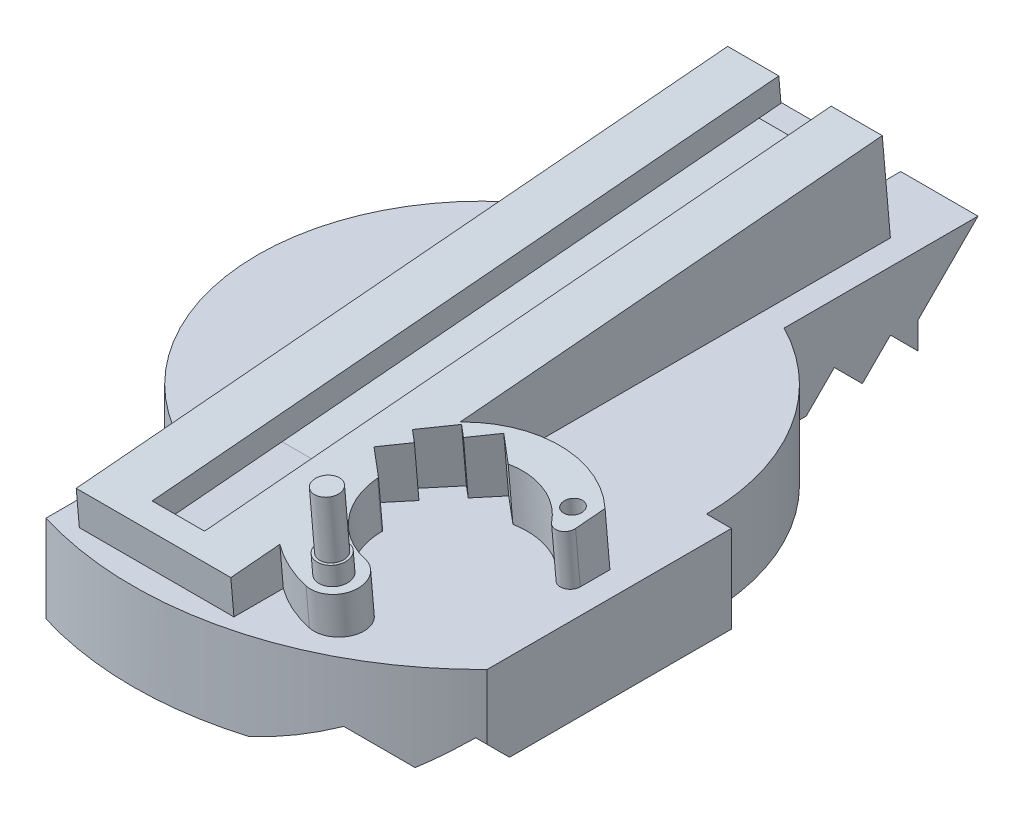
SolidWorks part; units mm, degrees
material "PLA"
ref_plane "Plan de face" through (0, 0, 0) normal (0, 0, 1) x (1, 0, 0)
ref_plane "Plan de dessus" through (0, 0, 0) normal (0, 1, 0) x (1, 0, 0)
ref_plane "Plan de droite" through (0, 0, 0) normal (1, 0, 0) x (0, 0, -1)
sketch "Esquisse1" plane through (0, 0, 0) normal (0, 1, 0) x (1, 0, 0)
  line L1 (-50, -70) -> (50, -70)
  line L2 (-50, -70) -> (-50, 70)
  line L3 (-50, 70) -> (50, 70)
  line L4 (50, -70) -> (50, 70)
  line L5 (-50, -70) -> (50, 70) construction
  line L6 (-50, 70) -> (50, -70) construction
  circle A0 centre (0, 0) radius 45
  point P0 (0, 0)
  dimension "D3" = 90
  dimension "D1" = 100
  dimension "D2" = 140
extrude "Boss.-Extru.1" add sketch "Esquisse1" along normal blind 12.5
sketch "Esquisse3" plane through (0, 12.5, 0) normal (0, 1, 0) x (1, 0, 0)
  line L1 (-50, -70) -> (50, -70)
  line L2 (-50, -70) -> (-50, 70)
  line L3 (-50, 70) -> (50, 70)
  line L4 (50, -70) -> (50, 70)
extrude "Boss.-Extru.2" add sketch "Esquisse3" along normal blind 5
sketch "Esquisse5" plane through (0, 17.5, 0) normal (0, 1, 0) x (1, 0, 0)
  line L0 (50, 0) -> (-50, 0) construction
  line L1 (50, -70) -> (50, 70) construction
  line L2 (-50, 70) -> (-50, -70) construction
ref_plane "Plan1" through (0, 0.1329, -1.5194) normal (0, 0.0872, -0.9962) x (-1, 0, 0)
sketch "Esquisse14" plane through (0, 17.5, 0) normal (0, 1, 0) x (1, 0, 0)
  line L0 (50, -30) -> (-50, -30) construction
  line L1 (50, -70) -> (50, 70) construction
  line L2 (-50, 70) -> (-50, -70) construction
  dimension "D1" = 30
ref_plane "Plan2" through (0, 19.9718, 1.7473) normal (0, -0.9962, -0.0872) x (-1, 0, 0)
sketch "Esquisse15" plane through (0, 9.8574, 117.3553) normal (0, 0.9962, 0.0872) x (1, 0, 0)
  line L0 (50, 87.689) -> (-50, 87.689) construction
  line L1 (-15.5, 87.689) -> (15.5, 87.689)
  line L2 (-15.5, 87.689) -> (-15.5, 183.689)
  line L3 (-15.5, 183.689) -> (15.5, 183.689)
  line L4 (15.5, 87.689) -> (15.5, 183.689)
  point P7 (0, 87.689)
  dimension "D1" = 31
  dimension "D2" = 96
extrude "Boss.-Extru.6" add sketch "Esquisse15" against normal up to surface up to face at (0, 17.5, 0)
sketch "Esquisse6" plane through (0, -4.4235, -1.9181) normal (0, -0.0872, 0.9962) x (1, 0, 0)
  line L0 (50, 22.0072) -> (-50, 22.0072) construction
  line L6 (15.5, 24.6219) -> (10.5, 24.6219)
  line L7 (15.5, 24.6219) -> (15.5, 34.8719)
  line L8 (15.5, 34.8719) -> (5.25, 34.8719)
  line L11 (5.25, 29.8719) -> (5.25, 34.8719)
  line L15 (0, -1.5271) -> (0, 34.8719) construction
  line L16 (50, -1.5271) -> (-50, -1.5271) construction
  line L17 (-5.25, 29.8719) -> (-5.25, 34.8719)
  line L18 (-15.5, 34.8719) -> (-5.25, 34.8719)
  line L19 (-15.5, 24.6219) -> (-15.5, 34.8719)
  line L20 (-15.5, 24.6219) -> (-10.5, 24.6219)
  line L23 (10.5, 24.6219) -> (5.25, 29.8719)
  line L24 (-5.25, 29.8719) -> (-10.5, 24.6219)
  line L26 (-15.5, 24.6219) -> (15.5, 24.6219) construction
  dimension "D1" = 10.25
  dimension "D2" = 5
  dimension "D3" = 5
  dimension "D4" = 45
  dimension "D5" = 10.5
extrude "Boss.-Extru.3" add sketch "Esquisse6" along normal blind 60 and the other way up to surface (66.1142 mm away) other way up to face at (0, 21.6835, -66.0007)
sketch "Esquisse7" plane through (0, -5.0964, 58.2523) normal (0, -0.0872, 0.9962) x (1, 0, 0)
  line L1 (-15.5, 30.2981) -> (15.5, 30.2981)
  line L2 (-15.5, 30.2981) -> (-15.5, 22.6827)
  line L3 (-15.5, 22.6827) -> (15.5, 22.6827)
  line L4 (15.5, 30.2981) -> (15.5, 22.6827)
extrude "Boss.-Extru.4" add sketch "Esquisse7" along normal blind 5
sketch "Esquisse16" plane through (0, 5.8952, -67.382) normal (0, 0.0872, -0.9962) x (-1, 0, 0)
  line L0 (-10.5, 20.0481) -> (-5.25, 25.2981)
  line L1 (-5.25, 25.2981) -> (-5.25, 30.2981)
  line L2 (-5.25, 30.2981) -> (5.25, 30.2981)
  line L3 (5.25, 30.2981) -> (5.25, 25.2981)
  line L4 (5.25, 25.2981) -> (10.5, 20.0481)
  line L5 (10.5, 20.0481) -> (-10.5, 20.0481)
extrude "Enlèv. mat.-Extru.3" cut sketch "Esquisse16" against normal up to surface (126.1142 mm away) up to face at (0, 20.8973, 60.5264)
chamfer "Chanfrein1" distance 13 angle 45 1 edges at (0, 12.5, 45)
sketch "Esquisse18" plane through (0, 12.5, 0) normal (0, -1, 0) x (-1, 0, 0)
  line L1 (-2.75, -1.5) -> (2.75, -1.5)
  line L2 (-2.75, -1.5) -> (-2.75, 1.5)
  line L3 (-2.75, 1.5) -> (2.75, 1.5)
  line L4 (2.75, -1.5) -> (2.75, 1.5)
  line L5 (-2.75, -1.5) -> (2.75, 1.5) construction
  line L6 (-2.75, 1.5) -> (2.75, -1.5) construction
  point P0 (0, 0)
  dimension "D1" = 3
  dimension "D2" = 5.5
extrude "Enlèv. mat.-Extru.5" cut sketch "Esquisse18" against normal blind 10
chamfer "Chanfrein2" distance 2 angle 45 2 edges at (0, 12.5, 1.5) (0, 12.5, -1.5)
sketch "Esquisse12" plane through (0, 17.5, 0) normal (0, 1, 0) x (1, 0, 0)
  line L0 (-15.5, 66.3667) -> (-15.5, -65.2483) construction
  line L5 (-50, 70) -> (-50, -70)
  line L6 (-50, -70) -> (-20.5, -70)
  line L10 (-20.5, 40.0593) -> (-20.5, 70)
  line L11 (-50, -70) -> (50, -70) construction
  line L12 (-20.5, -40.0593) -> (-20.5, -70)
  line L17 (0, -70) -> (0, 70) construction
  line L21 (-20.5, 70) -> (-50, 70)
  line L24 (-50, 70) -> (-50, -70) construction
  line L26 (50, 70) -> (-50, 70) construction
  line L32 (50, 70) -> (20.5, 70)
  line L33 (50, 70) -> (50, 0)
  line L34 (50, 0) -> (45, 0)
  line L35 (20.5, 70) -> (20.5, 40.0593)
  arc A1 (-20.5, 40.0593) -> (-20.5, -40.0593) centre (0, 0) ccw
  arc A3 (20.5, 40.0593) -> (45, 0) centre (0, 0) cw
  dimension "D3" = 45
  dimension "D1" = 5
extrude "Enlèv. mat.-Extru.1" cut sketch "Esquisse12" against normal through all both and the other way through all
sketch "Esquisse13" plane through (0, 0, 0) normal (1, 0, 0) x (0, 0, -1)
  line L0 (67, 0) -> (61.375, 5.625)
  line L1 (40.0593, 0) -> (70, 0) construction
  line L2 (61.375, 5.625) -> (55.75, 0)
  line L3 (55.75, 0) -> (50.125, 5.625)
  line L4 (50.125, 5.625) -> (44.5, 0)
  line L5 (-40.0593, 0) -> (40.0593, 0) construction
  line L6 (44.5, 0) -> (55.75, 0)
  line L7 (67, 0) -> (55.75, 0)
  line L9 (70, 0) -> (70, 17.5) construction
  line L10 (-44.5, 0) -> (44.5, 0) construction
  line L11 (0, 0) -> (0, 6.324) construction
  line L13 (-44.5, 0) -> (-55.75, 0)
  line L14 (-67, 0) -> (-55.75, 0)
  line L16 (-50.125, 5.625) -> (-44.5, 0)
  line L17 (-55.75, 0) -> (-50.125, 5.625)
  line L18 (-61.375, 5.625) -> (-55.75, 0)
  line L19 (-67, 0) -> (-61.375, 5.625)
  dimension "D1" = 3
  dimension "D3" = 45
extrude "Enlèv. mat.-Extru.2" cut sketch "Esquisse13" against normal through all both and the other way through all contours L17 L13 L16 | L19 L14 L18 | L3 L4 L6 | L7 L0 L2 region at (0, 1.875, 61.375) region at (0, 1.875, 50.125)
sketch "Esquisse17" plane through (0, 19.9718, 1.7473) normal (0, 0.9962, 0.0872) x (1, 0, 0)
  line L0 (15.5, 67.6394) -> (-15.5, 67.6394) construction
  line L1 (3.2, 62.9394) -> (-3.2, 62.9394)
  line L2 (3.2, 62.9394) -> (3.2, 66.3394)
  line L3 (3.2, 66.3394) -> (-3.2, 66.3394)
  line L4 (-3.2, 62.9394) -> (-3.2, 66.3394)
  line L5 (3.2, 62.9394) -> (-3.2, 66.3394) construction
  line L6 (3.2, 66.3394) -> (-3.2, 62.9394) construction
  point P0 (0, 64.6394)
  dimension "D1" = 3.4
  dimension "D2" = 3
  dimension "D3" = 6.4
extrude "Enlèv. mat.-Extru.4" cut sketch "Esquisse17" against normal blind 5
chamfer "Chanfrein3" distance 0.5 angle 45 4 edges at (3.2, 25.6055, -62.6461) (0, 25.4573, -60.9526) (0, 25.7536, -64.3396) (-3.2, 25.6055, -62.6461)
ref_axis "Axe1" through (0, 37.8818, 0) along (0, -1, 0)
sketch "Esquisse19" plane through (0, 17.5, 0) normal (0, 1, 0) x (1, 0, 0)
  line L0 (20.5, 66.9309) -> (-20.5, 66.9309)
  line L1 (20.5, 40.0593) -> (20.5, 70) construction
  line L2 (-20.5, 70) -> (-20.5, 40.0593) construction
  line L4 (20.5, 70) -> (-20.5, 70) construction
  arc A0 (-20.5, 66.9309) -> (20.5, 66.9309) centre (0, 0) ccw
extrude "Enlèv. mat.-Extru.6" cut sketch "Esquisse19" against normal through all flip side to cut
sketch "Esquisse20" plane through (0, 19.9718, 1.7473) normal (0, -0.9962, -0.0872) x (-1, 0, 0)
  line L1 (-27.3919, -19.5971) -> (-22.0295, -15.0976)
  line L3 (-15.5003, -33.7689) -> (-10.138, -29.2694)
  line L4 (-22.0295, -15.0976) -> (-18.3335, -19.5024)
  line L5 (-15.5, -63.4748) -> (-15.5, 67.6394) construction
  line L6 (-13.834, -24.8647) -> (-11.5359, -22.9363)
  line L7 (-50, -28.3606) -> (50, -28.3606) construction
  line L8 (-30, -33.8606) -> (-67.0315, -33.8606) construction
  line L9 (-18.3335, -19.5024) -> (-16.0354, -17.574)
  line L10 (-11.5359, -22.9363) -> (-16.0354, -17.574)
  line L11 (-30, -33.8606) -> (-11.0095, -17.9257) construction
  line L12 (-13.834, -24.8647) -> (-10.138, -29.2694)
  arc A0 (-27.3919, -19.5971) -> (-15.5003, -33.7689) centre (-30, -33.8606) ccw
  dimension "D1" = 14.5
  dimension "D4" = 5.5
  dimension "D2" = 18.5
  dimension "D3" = 7
  dimension "D5" = 40
  dimension "D6" = 7
  dimension "D7" = 3
extrude "Enlèv. mat.-Extru.7" cut sketch "Esquisse20" against normal through all and the other way blind 10
sketch "Esquisse21" plane through (0, 30.1828, 2.6407) normal (0, 0.9962, 0.0872) x (1, 0, 0)
  line L7 (45, -17.7667) -> (45, -23.6989)
  line L9 (62.3467, -18.0505) -> (62.3467, -56.0213) construction
  line L10 (35.8082, -55.0804) -> (62.3467, -56.0213) construction
  line L11 (34.809, -47.5402) -> (54.8467, -48.2507) construction
  line L12 (54.8467, -25.5505) -> (54.8467, -48.2507) construction
  line L13 (41.8828, -25.5505) -> (54.8467, -25.5505) construction
  line L14 (45.2988, -18.0505) -> (62.3467, -18.0505) construction
  line L15 (22.0295, -15.0976) -> (18.3335, -19.5024)
  line L16 (22.0295, -15.0976) -> (27.3916, -19.5969)
  line L17 (10.5, -29.5732) -> (15.5, -33.7687)
  line L18 (15.5, -33.7687) -> (15.5, -63.4748) construction
  line L19 (27.3919, -19.5971) -> (22.0295, -15.0976) construction
  line L20 (13.834, -24.8647) -> (11.1117, -22.5804)
  line L21 (18.3335, -19.5024) -> (16.0354, -17.574)
  line L22 (18.3335, -19.5024) -> (16.0354, -17.574) construction
  line L23 (13.834, -24.8647) -> (11.5359, -22.9363) construction
  line L24 (13.834, -24.8647) -> (10.5, -28.838)
  line L25 (15.5, -18.212) -> (16.0354, -17.574)
  line L26 (15.5, 67.6394) -> (15.5, -18.212) construction
  line L27 (15.5, -18.212) -> (15.5, -17.3148)
  line L28 (10.5, -48.6935) -> (10.5, -29.5732)
  line L29 (10.5, -29.5732) -> (10.5, -58.4748) construction
  line L30 (10.5, -28.838) -> (10.5, -23.6742)
  arc A0 (41.4243, -24.9306) -> (27.3916, -19.5969) centre (30, -33.8606) ccw
  arc A1 (11.1117, -22.5804) -> (10.5, -23.6742) centre (30, -33.8606) ccw
  arc A2 (45, -17.7667) -> (15.5, -17.3148) centre (30, -33.8606) ccw
  arc A3 (45.2988, -18.0505) -> (35.8082, -55.0804) centre (30, -33.8606) ccw construction
  arc A4 (41.8828, -25.5505) -> (34.809, -47.5402) centre (30, -33.8606) ccw construction
  arc A5 (45, -23.6989) -> (41.4243, -24.9306) centre (43, -23.6989) cw
  arc A6 (27.0256, -48.0526) -> (24.9744, -57.8399) centre (26, -52.9462) cw
  arc A7 (15.5, -33.7687) -> (27.0256, -48.0526) centre (30, -33.8606) ccw
  arc A8 (15.5, -33.8606) -> (27.3919, -19.5971) centre (30, -33.8606) ccw construction
  arc A10 (10.5, -48.6935) -> (24.9744, -57.8399) centre (30, -33.8606) ccw
  point P17 (26, -55.4918)
  point P32 (0, 0)
  dimension "D2" = 2
  dimension "D5" = 22.0003
  dimension "D6" = 5
  dimension "D3" = 15
  dimension "D4" = 4
  dimension "D1" = 7.5
extrude "Boss.-Extru.7" add sketch "Esquisse21" against normal up to surface (11.025 mm away) up to face at (9.7392, 17.5, -5.7302)
sketch "Esquisse22" plane through (0, 30.1828, 2.6407) normal (0, 0.9962, 0.0872) x (1, 0, 0)
  line L0 (18.7512, -47.2664) -> (41.2488, -20.4548) construction
  line L1 (30, -33.8606) -> (30, -23.5783) construction
  circle A0 centre (41.2488, -20.4548) radius 1.9
  circle A1 centre (18.7512, -47.2664) radius 1.9
  arc A3 (41.4243, -24.9306) -> (27.3916, -19.5969) centre (30, -33.8606) ccw construction
  point P4 (30, -33.8606)
  point P5 (30, -33.8606)
  dimension "D1" = 3.8
  dimension "D2" = 35
  dimension "D3" = 40
extrude "Enlèv. mat.-Extru.8" cut sketch "Esquisse22" against normal blind 10
sketch "Esquisse23" plane through (0, 30.1828, 2.6407) normal (0, 0.9962, 0.0872) x (1, 0, 0)
  circle A0 centre (26, -53.2748) radius 3
  circle A1 centre (26, -53.2748) radius 2.7 construction
  dimension "D1" = 6
extrude "Boss.-Extru.8" add sketch "Esquisse23" along normal blind 3.9
sketch "Esquisse24" plane through (0, 34.0679, 2.9806) normal (0, 0.9962, 0.0872) x (1, 0, 0)
  circle A0 centre (26, -53.2748) radius 2.5
  circle A1 centre (26, -53.2748) radius 3 construction
  dimension "D1" = 5
extrude "Boss.-Extru.9" add sketch "Esquisse24" along normal blind 12
sketch "Esquisse25" plane through (0, 0, 0) normal (1, 0, 0) x (0, 0, -1)
  line L0 (66.9309, 5.5) -> (78.9309, 17.5)
  line L1 (78.9309, 17.5) -> (66.9309, 17.5)
  line L2 (66.9309, 0.0691) -> (66.9309, 17.5) construction
  line L3 (66.9309, 17.5) -> (66.9309, 5.5)
  line L4 (-48.9898, 17.5) -> (-70, 17.5) construction
  line L7 (66.9309, 0.0691) -> (66.9309, 17.5) construction
  dimension "D1" = 45
  dimension "D2" = 12
extrude "Boss.-Extru.10" add sketch "Esquisse25" along normal up to surface and the other way up to surface up to face at (20.5, 5.7899, -53.2163) other way up to face at (-20.5, 5.7899, -53.2163)
sketch "Esquisse26" plane through (0, 0, 0) normal (1, 0, 0) x (0, 0, -1)
  line L0 (66.9309, 5.5) -> (78.9309, 17.5)
  line L1 (78.9309, 17.5) -> (66.9309, 17.5)
  line L3 (66.9309, 17.5) -> (66.9309, 5.5)
  line L6 (-48.9898, 17.5) -> (-70, 17.5) construction
  line L7 (66.9309, 0.0691) -> (66.9309, 5.5) construction
  line L8 (78.9309, 17.5) -> (66.9309, 5.5) construction
extrude "Enlèv. mat.-Extru.10" cut sketch "Esquisse26" against normal blind 5 and the other way blind 5
sketch "Esquisse27" plane through (0, 0, -66.9309) normal (0, 0, -1) x (-1, 0, 0)
  line L1 (-1, 0) -> (1, 0)
  line L2 (-1, 0) -> (-1, 15.4617)
  line L3 (-1, 15.4617) -> (1, 15.4617)
  line L4 (1, 0) -> (1, 15.4617)
  arc A0 (2.2789, 14.0766) -> (-2.4588, 14.8469) centre (-0.0899, 14.4617) ccw construction
  point P9 (0, 0)
  dimension "D1" = 2
  dimension "D2" = 1
extrude "Enlèv. mat.-Extru.11" cut sketch "Esquisse27" against normal up to surface (68.4309 mm away) up to face at (0, 17.2467, 1.5)
chamfer "Chanfrein4" distance 1 angle 45 2 edges at (-1, 15.4617, -34.2155) (1, 15.4617, -34.2155)
